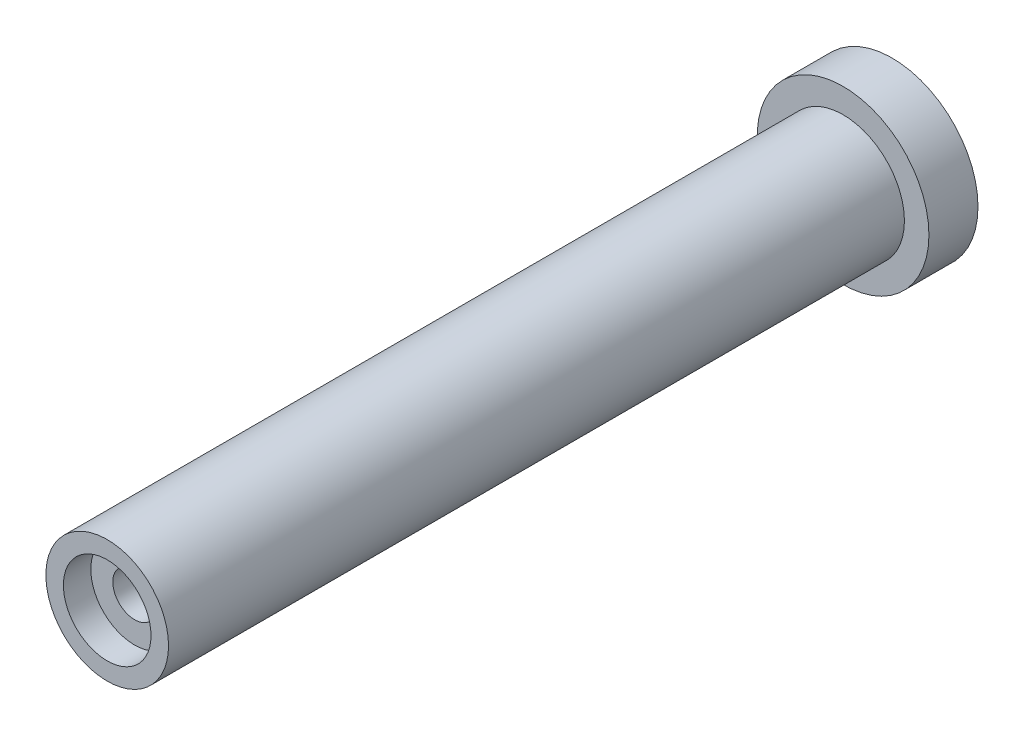
SolidWorks part; units mm, degrees
ref_plane "Plan de face" through (0, 0, 0) normal (0, 0, 1) x (1, 0, 0)
ref_plane "Plan de dessus" through (0, 0, 0) normal (0, 1, 0) x (1, 0, 0)
ref_plane "Plan de droite" through (0, 0, 0) normal (1, 0, 0) x (0, 0, -1)
sketch "Esquisse1" plane through (0, 0, 0) normal (0, 0, 1) x (1, 0, 0)
  circle A0 centre (0, 0) radius 2.5
  dimension "D1" = 5
extrude "Boss.-Extru.1" add sketch "Esquisse1" along normal blind 30
sketch "Esquisse2" plane through (0, 0, 0) normal (0, 0, 1) x (1, 0, 0)
  line L1 (-1.7187, 0.1158) -> (1.7187, 0.1158)
  line L2 (-1.7187, 0.1158) -> (-1.7187, -0.1158)
  line L3 (-1.7187, -0.1158) -> (1.7187, -0.1158)
  line L4 (1.7187, 0.1158) -> (1.7187, -0.1158)
  line L5 (-1.7187, 0.1158) -> (1.7187, -0.1158) construction
  line L6 (-1.7187, -0.1158) -> (1.7187, 0.1158) construction
  line L7 (-0.1158, -1.7187) -> (0.1158, -1.7187)
  line L8 (-0.1158, -1.7187) -> (-0.1158, 1.7187)
  line L9 (-0.1158, 1.7187) -> (0.1158, 1.7187)
  line L10 (0.1158, -1.7187) -> (0.1158, 1.7187)
  line L11 (-0.1158, -1.7187) -> (0.1158, 1.7187) construction
  line L12 (-0.1158, 1.7187) -> (0.1158, -1.7187) construction
  circle A0 centre (0, 0) radius 3.5
  point P11 (0, 0)
  dimension "D1" = 7
extrude "Boss.-Extru.2" add sketch "Esquisse2" against normal blind 2 contours A0 L10 L7 L8 L3 L2 L1 L9 L4 region at (-3.401, 0, 0)
hole_wizard "Chambrage pour vis à tête ronde bombée #01" positions "Esquisse19" profile "Esquisse17" counterbore size "#0" standard "Ansi Inch"
sketch "Esquisse19" plane through (0, 0, 30) normal (0, 0, 1) x (1, 0, 0)
  point P0 (0, 0)
sketch "Esquisse17" plane through (0, 0, 30) normal (1, 0, 0) x (0, -1, 0)
  line L0 (0, 0) -> (0, 6.5342)
  line L1 (0, 6.5342) -> (0.889, 6)
  line L2 (0.889, 6) -> (0.889, 1.1176)
  line L3 (0.889, 1.1176) -> (1.7856, 1.1176)
  line L4 (1.7856, 1.1176) -> (1.7856, 0)
  line L5 (1.7856, 0) -> (0, 0)
  line L10 (0, 6.5342) -> (-0.889, 6) construction
  line L11 (0, -6.35) -> (0, 107.95) construction
  dimension "Diamètre du perçage" = 1.778
  dimension "Profondeur du perçage" = 6
  dimension "Diamètre du chambrage" = 3.5712
  dimension "Profondeur du chambrage" = 1.1176
  dimension "Angle de pointe" = 118
